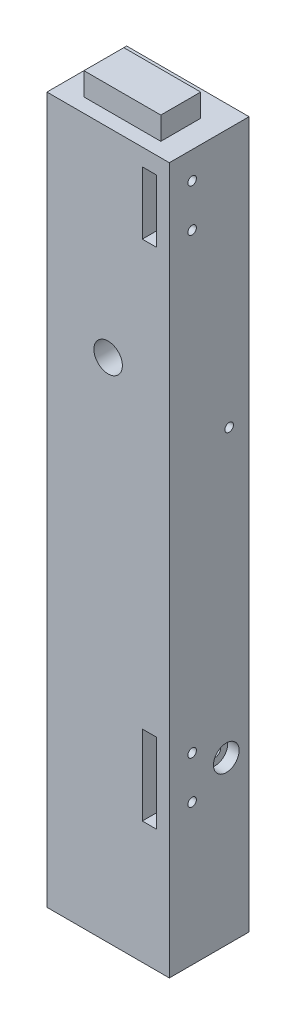
SolidWorks part; units mm, degrees
ref_plane "Front Plane" through (0, 0, 0) normal (0, 0, 1) x (1, 0, 0)
ref_plane "Top Plane" through (0, 0, 0) normal (0, 1, 0) x (1, 0, 0)
ref_plane "Right Plane" through (0, 0, 0) normal (1, 0, 0) x (0, 0, -1)
sketch "Sketch1" plane through (0, 0, 0) normal (0, 0, 1) x (1, 0, 0)
  line L1 (68.2625, 393.7) -> (-68.2625, 393.7)
  line L2 (68.2625, 393.7) -> (68.2625, -393.7)
  line L3 (68.2625, -393.7) -> (-68.2625, -393.7)
  line L4 (-68.2625, 393.7) -> (-68.2625, -393.7)
  line L5 (68.2625, 393.7) -> (-68.2625, -393.7) construction
  line L6 (68.2625, -393.7) -> (-68.2625, 393.7) construction
  point P0 (0, 0)
  dimension "D1" = 787.4
  dimension "D2" = 136.525
extrude "Boss-Extrude1" add sketch "Sketch1" along normal blind 88.9
sketch "Sketch2" plane through (0, 393.7, 0) normal (0, 1, 0) x (1, 0, 0)
  line L1 (-42.8625, -28.575) -> (42.8625, -28.575)
  line L2 (-42.8625, -28.575) -> (-42.8625, -73.025)
  line L3 (-42.8625, -73.025) -> (42.8625, -73.025)
  line L4 (42.8625, -28.575) -> (42.8625, -73.025)
  line L5 (-42.8625, -28.575) -> (42.8625, -73.025) construction
  line L6 (-42.8625, -73.025) -> (42.8625, -28.575) construction
  line L7 (68.2625, 0) -> (-68.2625, 0) construction
  line L8 (68.2625, -88.9) -> (68.2625, 0) construction
  point P0 (0, -50.8)
  dimension "D1" = 44.45
  dimension "D2" = 85.725
  dimension "D3" = 28.575
  dimension "D4" = 25.4
extrude "Boss-Extrude2" add sketch "Sketch2" along normal blind 25.4
sketch "Sketch4" plane through (0, 0, 0) normal (0, 0, -1) x (-1, 0, 0)
  line L0 (0, 0) -> (0, 50000) construction
  line L1 (-68.2625, 393.7) -> (68.2625, 393.7) construction
  line L3 (-22.225, 127) -> (22.225, 127)
  line L4 (-22.225, 127) -> (-22.225, -368.3)
  line L5 (-22.225, -368.3) -> (22.225, -368.3)
  line L6 (22.225, 127) -> (22.225, -368.3)
  line L7 (-22.225, 127) -> (22.225, -368.3) construction
  line L8 (-22.225, -368.3) -> (22.225, 127) construction
  line L9 (68.2625, -393.7) -> (-68.2625, -393.7) construction
  circle A0 centre (0, 171.45) radius 31.75
  circle A1 centre (0, 171.45) radius 15.875
  point P8 (0, -120.65)
  dimension "D5" = 63.5
  dimension "D6" = 31.75
  dimension "D1" = 222.25
  dimension "D2" = 44.45
  dimension "D3" = 44.45
  dimension "D4" = 25.4
extrude "Cut-Extrude1" cut sketch "Sketch4" against normal blind 44.45 contours L6 L5 L4 L3
extrude "Cut-Extrude2" cut sketch "Sketch4<3>" against normal blind 12.7 contours A1 | A0
sketch "Sketch4<3>" plane through (0, 0, 0) normal (0, 0, -1) x (-1, 0, 0) same geometry as "Sketch4"
extrude "Cut-Extrude3" cut sketch "Sketch4<4>" against normal through all contours A1 region at (0, 171.45, 0)
sketch "Sketch4<4>" plane through (0, 0, 0) normal (0, 0, -1) x (-1, 0, 0) same geometry as "Sketch4"
sketch "Sketch5" plane through (-68.2625, 0, 0) normal (-1, 0, 0) x (0, 0, 1)
  line L0 (0, 104.775) -> (44.45, 104.775) construction
  line L1 (60.325, -174.625) -> (15.875, -174.625)
  line L2 (60.325, -174.625) -> (60.325, -250.825)
  line L3 (60.325, -250.825) -> (15.875, -250.825)
  line L4 (15.875, -174.625) -> (15.875, -250.825)
  line L5 (60.325, -174.625) -> (15.875, -250.825) construction
  line L6 (60.325, -250.825) -> (15.875, -174.625) construction
  line L7 (0, 393.7) -> (0, -393.7) construction
  line L8 (88.9, -393.7) -> (0, -393.7) construction
  line L9 (22.225, 127) -> (22.225, 104.775) construction
  line L13 (0, 127) -> (0, -368.3)
  line L14 (44.45, 127) -> (0, 127)
  line L15 (44.45, -368.3) -> (44.45, 127)
  line L16 (0, -368.3) -> (44.45, -368.3)
  line L17 (0, 127) -> (0, -368.3)
  line L18 (44.45, 127) -> (0, 127)
  line L19 (44.45, -368.3) -> (44.45, 127)
  line L20 (0, -368.3) -> (44.45, -368.3)
  circle A0 centre (22.225, 104.775) radius 4.7625
  point P0 (38.1, -212.725)
  dimension "D7" = 9.525
  dimension "D1" = 44.45
  dimension "D2" = 15.875
  dimension "D3" = 142.875
  dimension "D4" = 76.2
  dimension "D6" = 22.225
  dimension "D5" = 0
extrude "Cut-Extrude4" cut sketch "Sketch5" against normal blind 19.05 contours L3 L19 L1 L4 | L19 L3 L2 L1 region at (-68.2625, -212.725, 52.3875) region at (-68.2625, -212.725, 30.1625)
extrude "Cut-Extrude5" cut sketch "Sketch5<3>" against normal through all contours A0
sketch "Sketch5<3>" plane through (-68.2625, 0, 0) normal (-1, 0, 0) x (0, 0, 1) same geometry as "Sketch5"
sketch "Sketch6" plane through (0, 0, 88.9) normal (0, 0, 1) x (1, 0, 0)
  line L0 (68.2625, -393.7) -> (68.2625, 393.7) construction
  line L1 (53.975, -168.275) -> (38.1, -168.275)
  line L2 (53.975, -168.275) -> (53.975, -257.175)
  line L3 (53.975, -257.175) -> (38.1, -257.175)
  line L4 (38.1, -168.275) -> (38.1, -257.175)
  line L5 (53.975, -168.275) -> (38.1, -257.175) construction
  line L6 (53.975, -257.175) -> (38.1, -168.275) construction
  line L7 (53.975, 374.65) -> (38.1, 374.65)
  line L8 (53.975, 374.65) -> (53.975, 304.8)
  line L9 (53.975, 304.8) -> (38.1, 304.8)
  line L10 (38.1, 374.65) -> (38.1, 304.8)
  line L11 (53.975, 374.65) -> (38.1, 304.8) construction
  line L12 (53.975, 304.8) -> (38.1, 374.65) construction
  line L13 (-68.2625, -393.7) -> (68.2625, -393.7) construction
  line L14 (68.2625, 393.7) -> (-68.2625, 393.7) construction
  point P0 (46.0375, -212.725)
  point P5 (46.0375, 339.725)
  dimension "D1" = 14.2875
  dimension "D2" = 15.875
  dimension "D3" = 88.9
  dimension "D4" = 136.525
  dimension "D5" = 15.875
  dimension "D6" = 19.05
  dimension "D7" = 69.85
extrude "Cut-Extrude6" cut sketch "Sketch6" against normal blind 50.8
sketch "Sketch7" plane through (68.2625, 0, 0) normal (1, 0, 0) x (0, 0, -1)
  line L0 (-88.9, 304.8) -> (-88.9, 374.65) construction
  line L1 (-88.9, 374.65) -> (-38.1, 374.65) construction
  line L2 (-38.1, 374.65) -> (-38.1, 304.8) construction
  line L3 (-38.1, 304.8) -> (-88.9, 304.8) construction
  line L4 (-88.9, -257.175) -> (-88.9, -168.275) construction
  line L5 (-88.9, -168.275) -> (-38.1, -168.275) construction
  line L6 (-38.1, -168.275) -> (-38.1, -257.175) construction
  line L7 (-38.1, -257.175) -> (-88.9, -257.175) construction
  line L8 (-88.9, 304.8) -> (-88.9, 374.65)
  line L9 (-88.9, 374.65) -> (-38.1, 374.65)
  line L10 (-38.1, 374.65) -> (-38.1, 304.8)
  line L11 (-38.1, 304.8) -> (-88.9, 304.8)
  line L12 (-88.9, -257.175) -> (-88.9, -168.275)
  line L13 (-88.9, -168.275) -> (-38.1, -168.275)
  line L14 (-38.1, -168.275) -> (-38.1, -257.175)
  line L15 (-38.1, -257.175) -> (-88.9, -257.175)
  line L16 (-63.5, 374.65) -> (-63.5, 304.8) construction
  line L17 (-63.5, -168.275) -> (-63.5, -257.175) construction
  circle A0 centre (-63.5, -188.9125) radius 4.7625
  circle A1 centre (-63.5, -236.5375) radius 4.7625
  circle A2 centre (-63.5, 363.5375) radius 4.7625
  circle A3 centre (-63.5, 315.9125) radius 4.7625
  point P16 (-63.5, -212.725)
  point P21 (-63.5, 339.725)
  dimension "D1" = 9.525
  dimension "D3" = 23.8125
  dimension "D5" = 23.8125
  dimension "D2" = 23.8125
  dimension "D4" = 25.4
  dimension "D6" = 23.8125
extrude "Cut-Extrude7" cut sketch "Sketch7" against normal blind 44.45 contours A2 | A3 | A1 | A0
sketch "Sketch8" plane through (68.2625, 0, 0) normal (1, 0, 0) x (0, 0, -1)
  line L0 (-60.325, -212.725) -> (-15.875, -212.725) construction
  line L4 (-60.325, -250.825) -> (-15.875, -250.825)
  line L5 (-60.325, -174.625) -> (-60.325, -250.825)
  line L6 (-15.875, -174.625) -> (-60.325, -174.625)
  line L7 (-15.875, -250.825) -> (-15.875, -174.625)
  line L8 (-60.325, -250.825) -> (-15.875, -250.825)
  line L9 (-60.325, -174.625) -> (-60.325, -250.825)
  line L10 (-15.875, -174.625) -> (-60.325, -174.625)
  line L11 (-15.875, -250.825) -> (-15.875, -174.625)
  circle A0 centre (-25.4, -212.725) radius 14.2875
  circle A1 centre (-25.4, -212.725) radius 6.35
  point P9 (-30.2086, -212.725)
  dimension "D3" = 12.7
  dimension "D4" = 28.575
  dimension "D2" = 9.525
  dimension "D1" = 0
extrude "Cut-Extrude8" cut sketch "Sketch8" against normal blind 12.7 contours L0 A0 L11 A1 | L11 A0 | A0 L0 A1 L11 region at (68.2625, -205.3904, 27.2119) region at (68.2625, -220.0596, 27.2119) region at (68.2625, -212.725, 13.9399)
extrude "Cut-Extrude9" cut sketch "Sketch8<3>" against normal through all contours L0 A1 | A1 L0 region at (68.2625, -215.42, 25.4) region at (68.2625, -210.03, 25.4)
sketch "Sketch8<3>" plane through (68.2625, 0, 0) normal (1, 0, 0) x (0, 0, -1) same geometry as "Sketch8"
